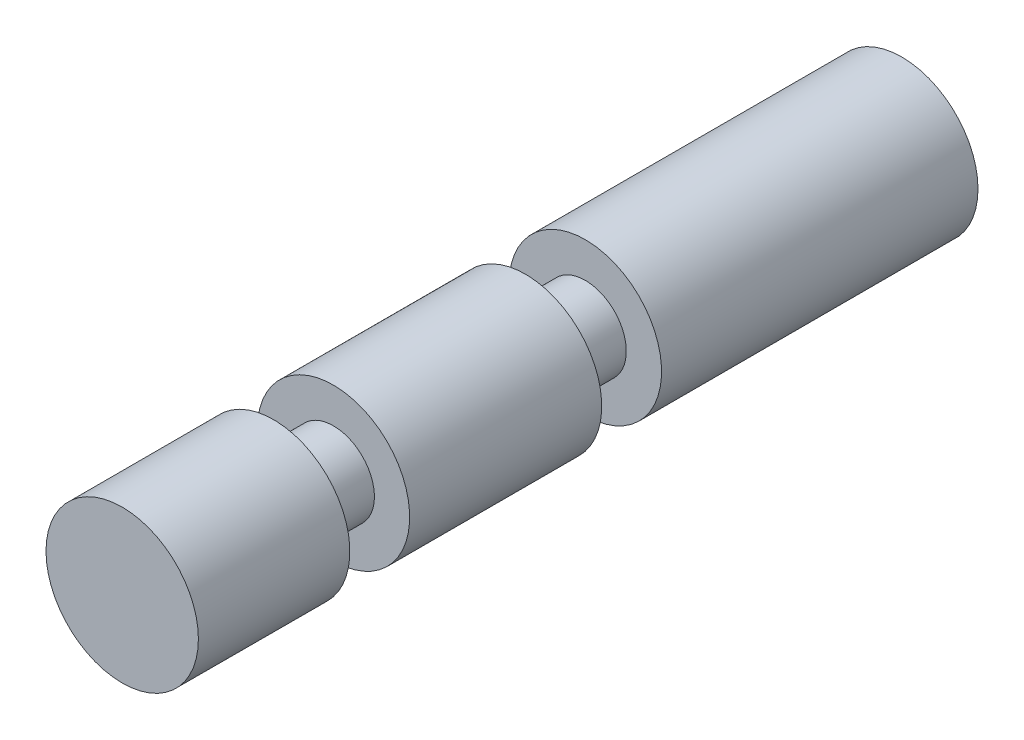
SolidWorks part; units mm, degrees
material "AISI 1015 Steel, Cold Drawn (SS)"
ref_plane "Front Plane" through (0, 0, 0) normal (0, 0, 1) x (1, 0, 0)
ref_plane "Top Plane" through (0, 0, 0) normal (0, 1, 0) x (1, 0, 0)
ref_plane "Right Plane" through (0, 0, 0) normal (1, 0, 0) x (0, 0, -1)
sketch "Sketch1" plane through (0, 0, 0) normal (0, 0, 1) x (1, 0, 0)
  circle A0 centre (0, 0) radius 3.0734
  dimension "D1" = 6.1468
extrude "Boss-Extrude1" add sketch "Sketch1" along normal blind 31.4452
sketch "Sketch3" plane through (0, 0, 0) normal (0, 1, 0) x (1, 0, 0)
  circle A0 centre (0, -3.175) radius 1.397
  dimension "D1" = 2.794
  dimension "D2" = 3.175
extrude "Cut-Extrude1" [suppressed] cut sketch "Sketch3" against normal through all and the other way through all
sketch "Sketch4" plane through (0, 0, 0) normal (1, 0, 0) x (0, 0, -1)
  line L0 (0, 0) -> (-31.4452, 0) construction
  line L1 (-13.97, 0) -> (-13.97, 2.3622) construction
  line L2 (0, 3.0734) -> (-31.4452, 3.0734) construction
  line L3 (-15.1765, 3.0734) -> (-12.7635, 3.0734)
  line L4 (-31.4452, 3.0734) -> (-31.4452, -3.0734) construction
  line L5 (-15.1765, 3.0734) -> (-15.1765, 1.651)
  line L6 (-15.1765, 1.651) -> (-12.7635, 1.651)
  line L7 (-12.7635, 3.0734) -> (-12.7635, 1.651)
  line L8 (-15.1765, 3.0734) -> (-12.7635, 1.651) construction
  line L9 (-15.1765, 1.651) -> (-12.7635, 3.0734) construction
  point P3 (-13.97, 0)
  dimension "D1" = 13.97
  dimension "D2" = 1.4224
  dimension "D3" = 2.413
sketch "Sketch6" plane through (0, 0, 0) normal (0, 0, -1) x (-1, 0, 0)
  circle A0 centre (0, 0) radius 0.635
  dimension "D1" = 1.27
extrude "Cut-Extrude2" [suppressed] cut sketch "Sketch6" against normal up to surface (35.56 mm away) up to face at (3.0734, 0, 31.4452)
sketch "Sketch9" plane through (0, 0, 0) normal (0, 0, -1) x (-1, 0, 0)
  circle A0 centre (0, 0) radius 1.397
extrude "Cut-Extrude3" cut sketch "Sketch9" against normal blind 7.62
revolve "Cut-Revolve1" cut sketch "Sketch4" angle 360 about L0
pattern_linear "LPattern1" count 2 spacing 10.16 along (0, 0, 1) of "Cut-Revolve1"
equation "\"D1@Boss-Extrude1\"=0.125+0.5 +0.1 + 0.35 -0.2+ 0.0625"
